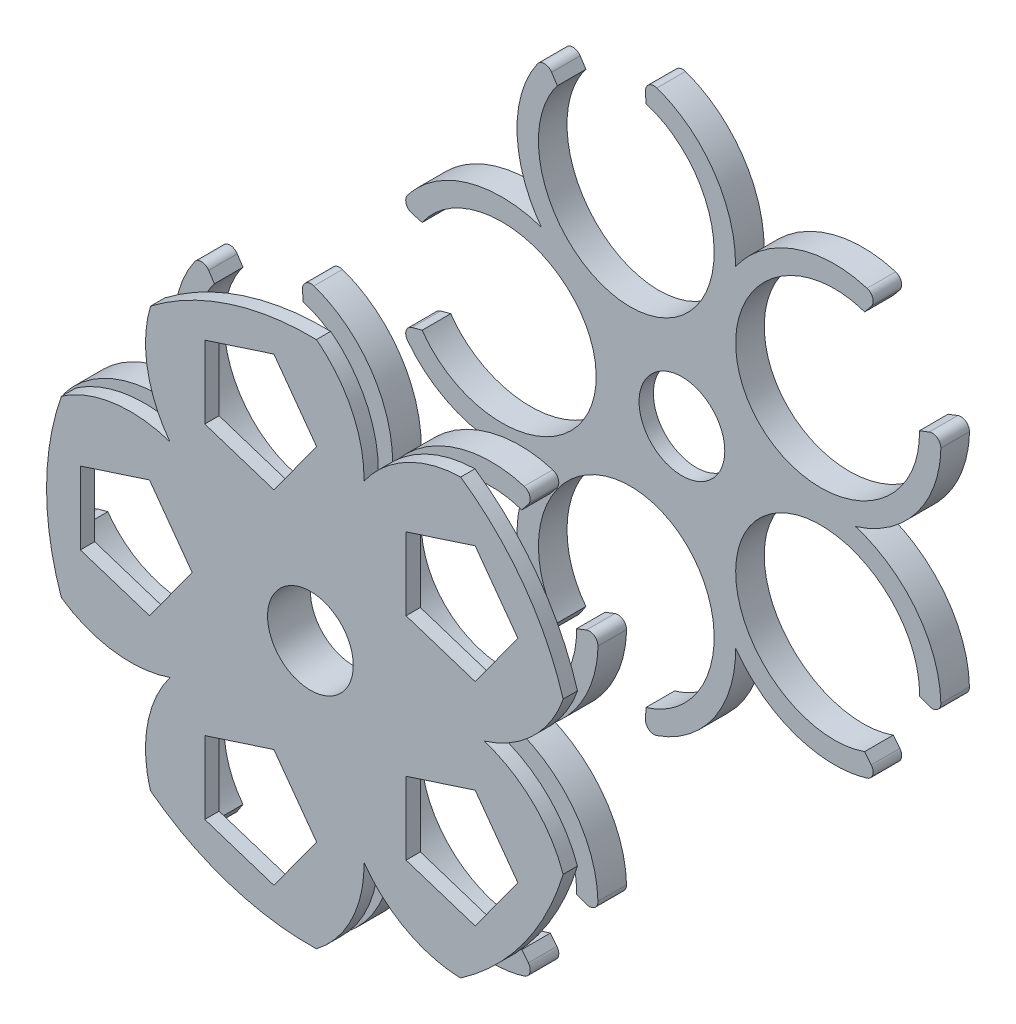
SolidWorks part; units mm, degrees
ref_plane "Front" through (0, 0, 0) normal (0, 0, 1) x (1, 0, 0)
ref_plane "Top" through (0, 0, 0) normal (0, 1, 0) x (1, 0, 0)
ref_plane "Right" through (0, 0, 0) normal (1, 0, 0) x (0, 0, -1)
sketch "Sketch1" plane through (0, 0, 0) normal (0, 0, 1) x (1, 0, 0)
  line L0 (0, 0) -> (-63, 0) construction
  line L1 (-63, 30.5) -> (-63, 38) construction
  line L2 (-103.5, 0) -> (-96, 0) construction
  line L3 (-30, 0) -> (-94.428, 17.2634) construction
  line L4 (-30, 0) -> (-94.428, -17.2634) construction
  line L5 (-94.428, 17.2634) -> (-94.428, -17.2634) construction
  line L6 (-90.8829, 16.3135) -> (-94.428, 17.2634)
  line L7 (-90.8829, -16.3135) -> (-94.428, -17.2634)
  arc A0 (-96.0456, -21.9691) -> (-94.428, -17.2634) centre (-93.6516, -20.1612) cw
  arc A1 (-94.428, 17.2634) -> (-96.0456, 21.9691) centre (-93.6516, 20.1612) cw
  ellipse E0 centre (-63, 0) end of major axis (-30, 0) minor radius 30.5 (-90.8829, -16.3135) -> (-90.8829, 16.3135) ccw
  ellipse E1 centre (-63, 0) end of major axis (-22.5, 0) minor radius 38 (-96.0456, -21.9691) -> (-96.0456, 21.9691) ccw
  dimension "D6" = 3
  dimension "D1" = 66
  dimension "D2" = 61
  dimension "D3" = 30
  dimension "D4" = 7.5
  dimension "D5" = 15
extrude "Boss-Extrude1" add sketch "Sketch1" along normal blind 10
sketch "Sketch3" plane through (0, 0, 0) normal (1, 0, 0) x (0, 0, -1)
  line L0 (0, 0) -> (-100, 0) construction
  dimension "D1" = 100
pattern_circular "CirPattern1" count 5 over 360 about axis through (0, 0, 0) along (0, 0, 1) reverse direction yes of bodies 103
sketch "Sketch4" plane through (0, 0, 10) normal (0, 0, 1) x (1, 0, 0)
  line L0 (-12.5693, -91.4759) -> (-12.7614, -95.1411) construction
  line L1 (-45.5984, -84.4717) -> (-43.5994, -81.3936) construction
  line L2 (83.1146, -40.2217) -> (86.5411, -41.537) construction
  line L3 (66.2467, -69.4698) -> (63.9369, -66.6175) construction
  line L4 (63.9369, 66.6175) -> (66.2467, 69.4698) construction
  line L5 (86.5411, 41.537) -> (83.1146, 40.2217) construction
  line L6 (-43.5994, 81.3936) -> (-45.5984, 84.4717) construction
  line L7 (-12.7614, 95.1411) -> (-12.5693, 91.4759) construction
  line L8 (-90.8829, -16.3135) -> (-94.428, -17.2634) construction
  line L9 (-94.428, 17.2634) -> (-90.8829, 16.3135) construction
  line L10 (-12.5693, -91.4759) -> (-12.7614, -95.1411)
  line L11 (-45.5984, -84.4717) -> (-43.5994, -81.3936)
  line L12 (83.1146, -40.2217) -> (86.5411, -41.537)
  line L13 (66.2467, -69.4698) -> (63.9369, -66.6175)
  line L14 (63.9369, 66.6175) -> (66.2467, 69.4698)
  line L15 (86.5411, 41.537) -> (83.1146, 40.2217)
  line L16 (-43.5994, 81.3936) -> (-45.5984, 84.4717)
  line L17 (-12.7614, 95.1411) -> (-12.5693, 91.4759)
  line L18 (-90.8829, -16.3135) -> (-94.428, -17.2634)
  line L19 (-94.428, 17.2634) -> (-90.8829, 16.3135)
  arc A0 (-12.7614, -95.1411) -> (-8.7859, -98.1336) centre (-9.7655, -95.2981) ccw construction
  arc A1 (-50.5736, -84.556) -> (-45.5984, -84.4717) centre (-48.1144, -82.8378) ccw construction
  arc A2 (86.5411, -41.537) -> (90.6157, -38.6808) centre (87.6162, -38.7362) ccw construction
  arc A3 (64.7894, -74.2276) -> (66.2467, -69.4698) centre (63.9152, -71.3578) ccw construction
  arc A4 (66.2467, 69.4698) -> (64.7894, 74.2276) centre (63.9152, 71.3578) ccw construction
  arc A5 (90.6157, 38.6808) -> (86.5411, 41.537) centre (87.6162, 38.7362) ccw construction
  arc A6 (-45.5984, 84.4717) -> (-50.5736, 84.556) centre (-48.1144, 82.8378) ccw construction
  arc A7 (-8.7859, 98.1336) -> (-12.7614, 95.1411) centre (-9.7655, 95.2981) ccw construction
  arc A8 (-94.428, -17.2634) -> (-96.0456, -21.9691) centre (-93.6516, -20.1612) ccw construction
  arc A9 (-96.0456, 21.9691) -> (-94.428, 17.2634) centre (-93.6516, 20.1612) ccw construction
  arc A10 (-12.7614, -95.1411) -> (-8.7859, -98.1336) centre (-9.7655, -95.2981) ccw
  arc A11 (-50.5736, -84.556) -> (-45.5984, -84.4717) centre (-48.1144, -82.8378) ccw
  arc A12 (86.5411, -41.537) -> (90.6157, -38.6808) centre (87.6162, -38.7362) ccw
  arc A13 (64.7894, -74.2276) -> (66.2467, -69.4698) centre (63.9152, -71.3578) ccw
  arc A14 (66.2467, 69.4698) -> (64.7894, 74.2276) centre (63.9152, 71.3578) ccw
  arc A15 (90.6157, 38.6808) -> (86.5411, 41.537) centre (87.6162, 38.7362) ccw
  arc A16 (-45.5984, 84.4717) -> (-50.5736, 84.556) centre (-48.1144, 82.8378) ccw
  arc A17 (-8.7859, 98.1336) -> (-12.7614, 95.1411) centre (-9.7655, 95.2981) ccw
  arc A18 (-94.428, -17.2634) -> (-96.0456, -21.9691) centre (-93.6516, -20.1612) ccw
  arc A19 (-96.0456, 21.9691) -> (-94.428, 17.2634) centre (-93.6516, 20.1612) ccw
  circle A20 centre (0, 0) radius 15
  ellipse E1 centre (-19.4681, -59.9166) end of major axis (-6.9529, -21.3988) minor radius 38 (-8.7859, -98.1336) -> (-50.5736, -84.556) ccw construction
  ellipse E3 centre (50.9681, -37.0305) end of major axis (18.2029, -13.2252) minor radius 38 (90.6157, -38.6808) -> (64.7894, -74.2276) ccw construction
  ellipse E5 centre (50.9681, 37.0305) end of major axis (18.2029, 13.2252) minor radius 38 (64.7894, 74.2276) -> (90.6157, 38.6808) ccw construction
  ellipse E7 centre (-19.4681, 59.9166) end of major axis (-6.9529, 21.3988) minor radius 38 (-50.5736, 84.556) -> (-8.7859, 98.1336) ccw construction
  ellipse E9 centre (-63, 0) end of major axis (-103.5, 0) minor radius 38 (-96.0456, -21.9691) -> (-96.0456, 21.9691) ccw construction
  ellipse E11 centre (-19.4681, -59.9166) end of major axis (-6.9529, -21.3988) minor radius 38 (11.3143, -34.8217) -> (-29.6211, -21.521) ccw
  ellipse E13 centre (50.9681, -37.0305) end of major axis (18.2029, -13.2252) minor radius 38 (36.6137, 0) -> (11.3143, -34.8217) ccw
  ellipse E15 centre (50.9681, 37.0305) end of major axis (18.2029, 13.2252) minor radius 38 (11.3143, 34.8217) -> (36.6137, 0) ccw
  ellipse E17 centre (-19.4681, 59.9166) end of major axis (-6.9529, 21.3988) minor radius 38 (-29.6211, 21.521) -> (11.3143, 34.8217) ccw
  ellipse E19 centre (-63, 0) end of major axis (-103.5, 0) minor radius 38 (-29.6211, -21.521) -> (-29.6211, 21.521) ccw
  ellipse M4 centre (-19.4681, 59.9166) end of major axis (-6.9529, 21.3988) minor radius 38 (-50.5736, 84.556) -> (-8.7859, 98.1336) ccw
  dimension "D1" = 30
extrude "Boss-Extrude2" add sketch "Sketch4" against normal blind 5 contours E19 E11 E13 E15 A20 M4 region at (-6.6559, -20.4847, 10)
pattern_linear "LPattern1" count 2 spacing 120 along (0, 0, 1) of bodies 108
sketch "Sketch5" plane through (0, 0, 130) normal (0, 0, 1) x (1, 0, 0)
  line L0 (0, 0) -> (18.773, 57.7774) construction
  line L1 (9.5492, 29.3893) -> (-25, 18.1636)
  line L2 (-25, 18.1636) -> (-25, -18.1636)
  line L3 (-25, -18.1636) -> (9.5492, -29.3893)
  line L4 (9.5492, -29.3893) -> (30.9017, 0)
  line L5 (30.9017, 0) -> (9.5492, 29.3893)
  circle A0 centre (0, 0) radius 25 construction
  circle A1 centre (0, 0) radius 15
  dimension "D1" = 50
extrude "Boss-Extrude3" add sketch "Sketch5" along normal blind 5
sketch "Sketch6" plane through (0, 0, 135) normal (0, 0, 1) x (1, 0, 0)
  line L0 (2.1631, 59.9166) -> (-12.7837, 80.489)
  line L1 (-41.3688, 0) -> (-56.3156, 20.5725)
  line L2 (-56.3156, 20.5725) -> (-80.5, 12.7145)
  line L3 (-80.5, 12.7145) -> (-80.5, -12.7145)
  line L4 (-80.5, -12.7145) -> (-56.3156, -20.5725)
  line L5 (-56.3156, -20.5725) -> (-41.3688, 0)
  line L6 (-12.7837, 39.3441) -> (2.1631, 59.9166)
  line L7 (-36.9681, 47.2021) -> (-12.7837, 39.3441)
  line L8 (-36.9681, 72.6311) -> (-36.9681, 47.2021)
  line L9 (-12.7837, 80.489) -> (-36.9681, 72.6311)
  line L10 (57.6525, 16.458) -> (72.5993, 37.0305)
  line L11 (33.4681, 24.316) -> (57.6525, 16.458)
  line L12 (33.4681, 49.745) -> (33.4681, 24.316)
  line L13 (57.6525, 57.603) -> (33.4681, 49.745)
  line L14 (72.5993, 37.0305) -> (57.6525, 57.603)
  line L15 (33.4681, -49.745) -> (57.6525, -57.603)
  line L16 (33.4681, -24.316) -> (33.4681, -49.745)
  line L17 (57.6525, -16.458) -> (33.4681, -24.316)
  line L18 (72.5993, -37.0305) -> (57.6525, -16.458)
  line L19 (57.6525, -57.603) -> (72.5993, -37.0305)
  line L20 (-36.9681, -47.2021) -> (-36.9681, -72.6311)
  line L21 (-12.7837, -39.3441) -> (-36.9681, -47.2021)
  line L22 (2.1631, -59.9166) -> (-12.7837, -39.3441)
  line L23 (-12.7837, -80.489) -> (2.1631, -59.9166)
  line L24 (-36.9681, -72.6311) -> (-12.7837, -80.489)
  arc A0 (-55.9425, -73.4593) -> (2.0801, -92.312) centre (0, 0) ccw
  arc A2 (52.5767, -75.9046) -> (88.4367, -26.5476) centre (0, 0) ccw
  arc A3 (88.4367, 26.5476) -> (52.5767, 75.9046) centre (0, 0) ccw
  arc A4 (2.0801, 92.312) -> (-55.9425, 73.4593) centre (0, 0) ccw
  arc A5 (-87.1511, 30.5043) -> (-87.1511, -30.5043) centre (0, 0) ccw
  circle A6 centre (0, 0) radius 15 construction
  circle A7 centre (0, 0) radius 15
  circle A8 centre (-63, 0) radius 17.5 construction
  ellipse E0 centre (-19.4681, 59.9166) end of major axis (-6.9529, 21.3988) minor radius 38 (18.773, 57.7774) -> (-8.7859, 98.1336) ccw construction
  ellipse E1 centre (50.9681, 37.0305) end of major axis (18.2029, 13.2252) minor radius 38 (64.7894, 74.2276) -> (18.773, 57.7774) ccw construction
  ellipse E2 centre (50.9681, 37.0305) end of major axis (18.2029, 13.2252) minor radius 38 (60.7507, 0) -> (90.6157, 38.6808) ccw construction
  ellipse E3 centre (50.9681, -37.0305) end of major axis (18.2029, -13.2252) minor radius 38 (90.6157, -38.6808) -> (60.7507, 0) ccw construction
  ellipse E4 centre (50.9681, -37.0305) end of major axis (18.2029, -13.2252) minor radius 38 (18.773, -57.7774) -> (64.7894, -74.2276) ccw construction
  ellipse E5 centre (-19.4681, -59.9166) end of major axis (-31.9833, -98.4343) minor radius 38 (-8.7859, -98.1336) -> (18.773, -57.7774) ccw construction
  ellipse E6 centre (-19.4681, -59.9166) end of major axis (-31.9833, -98.4343) minor radius 38 (-49.1484, -35.7084) -> (-50.5736, -84.556) ccw construction
  ellipse E7 centre (-63, 0) end of major axis (-103.5, 0) minor radius 38 (-96.0456, -21.9691) -> (-49.1484, -35.7084) ccw construction
  ellipse E8 centre (-63, 0) end of major axis (-103.5, 0) minor radius 38 (-49.1484, 35.7084) -> (-96.0456, 21.9691) ccw construction
  ellipse E9 centre (-19.4681, 59.9166) end of major axis (-6.9529, 21.3988) minor radius 38 (-50.5736, 84.556) -> (-49.1484, 35.7084) ccw construction
  ellipse E10 centre (-19.4681, 59.9166) end of major axis (-6.9529, 21.3988) minor radius 38 (18.773, 57.7774) -> (2.0801, 92.312) ccw
  ellipse E11 centre (50.9681, 37.0305) end of major axis (18.2029, 13.2252) minor radius 38 (52.5767, 75.9046) -> (18.773, 57.7774) ccw
  ellipse E12 centre (50.9681, 37.0305) end of major axis (18.2029, 13.2252) minor radius 38 (60.7507, 0) -> (88.4367, 26.5476) ccw
  ellipse E13 centre (50.9681, -37.0305) end of major axis (18.2029, -13.2252) minor radius 38 (88.4367, -26.5476) -> (60.7507, 0) ccw
  ellipse E14 centre (50.9681, -37.0305) end of major axis (18.2029, -13.2252) minor radius 38 (18.773, -57.7774) -> (52.5767, -75.9046) ccw
  ellipse E15 centre (-19.4681, -59.9166) end of major axis (-31.9833, -98.4343) minor radius 38 (2.0801, -92.312) -> (18.773, -57.7774) ccw
  ellipse E16 centre (-19.4681, -59.9166) end of major axis (-31.9833, -98.4343) minor radius 38 (-49.1484, -35.7084) -> (-55.9425, -73.4593) ccw
  ellipse E17 centre (-63, 0) end of major axis (-103.5, 0) minor radius 38 (-87.1511, -30.5043) -> (-49.1484, -35.7084) ccw
  ellipse E18 centre (-63, 0) end of major axis (-103.5, 0) minor radius 38 (-49.1484, 35.7084) -> (-87.1511, 30.5043) ccw
  ellipse E19 centre (-19.4681, 59.9166) end of major axis (-6.9529, 21.3988) minor radius 38 (-55.9425, 73.4593) -> (-49.1484, 35.7084) ccw
  point P143 (0, 0)
  dimension "D1" = 35
  dimension "D2" = 5
extrude "Boss-Extrude4" add sketch "Sketch6" along normal blind 5
